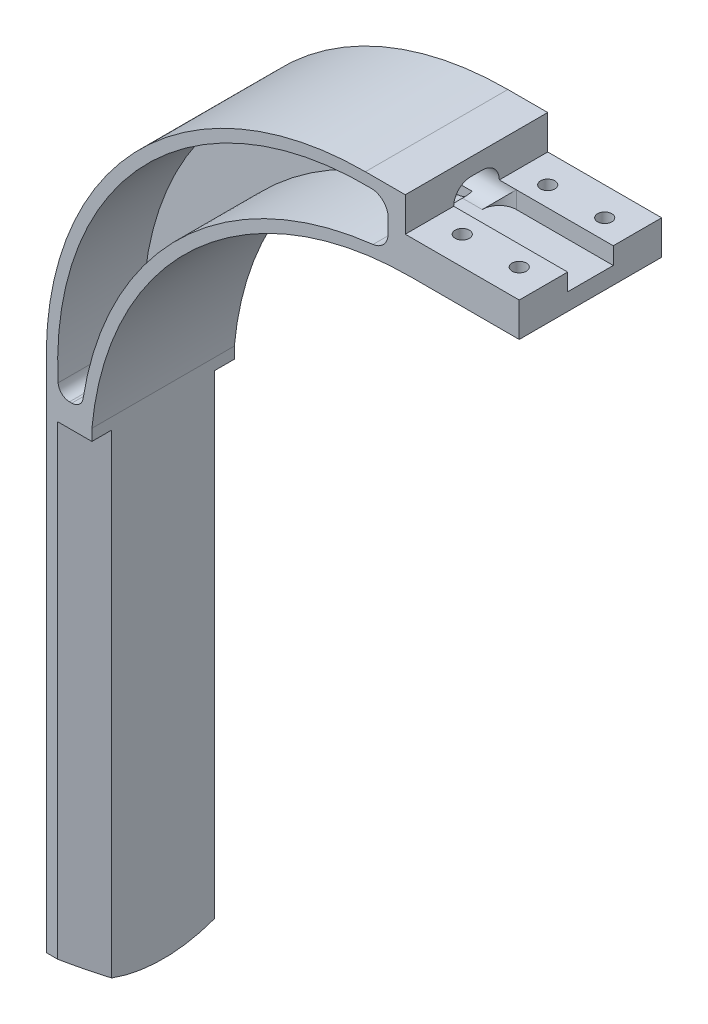
SolidWorks part; units mm, degrees
material "Сплав 2024"
ref_plane "Спереди" through (0, 0, 0) normal (0, 0, 1) x (1, 0, 0)
ref_plane "Сверху" through (0, 0, 0) normal (0, 1, 0) x (1, 0, 0)
ref_plane "Справа" through (0, 0, 0) normal (1, 0, 0) x (0, 0, -1)
sketch "Эскиз1" plane through (0, 0, 0) normal (0, 0, 1) x (1, 0, 0)
  line L0 (0, 0) -> (0, 95)
  line L1 (0, 0) -> (8, 0)
  line L2 (-20.7345, 150) -> (144.5665, 150) construction
  line L3 (83, 163.3115) -> (83, 122.0175) construction
  line L4 (8, 0) -> (8, 87)
  line L6 (83, 150) -> (56, 150)
  line L7 (83, 150) -> (83, 138)
  line L8 (83, 138) -> (64, 138)
  arc A0 (64, 138) -> (8, 87) centre (64, 81.7549) ccw
  arc A1 (56, 150) -> (0, 95) centre (56, 93.9909) ccw
  dimension "D1" = 95
  dimension "D2" = 87
  dimension "D3" = 150
  dimension "D4" = 83
  dimension "D5" = 8
  dimension "D6" = 12
  dimension "D7" = 27
  dimension "D8" = 19
extrude "Бобышка-Вытянуть1" add sketch "Эскиз1" along normal blind 25
sketch "Эскиз2" plane through (0, 0, 25) normal (0, 0, 1) x (1, 0, 0)
  line L1 (83, 150) -> (63, 150)
  line L2 (83, 150) -> (83, 144)
  line L3 (83, 144) -> (63, 144)
  line L4 (63, 150) -> (63, 144)
  dimension "D1" = 20
  dimension "D2" = 6
extrude "Вырез-Вытянуть1" cut sketch "Эскиз2" against normal through all
sketch "Эскиз5" plane through (0, 0, 0) normal (0, -1, 0) x (1, 0, 0)
  line L0 (8, 3.4641) -> (2, 0)
  line L1 (8, 25) -> (8, 0) construction
  line L2 (8, 3.4641) -> (10.1941, 4.7308)
  line L3 (2, 0) -> (8, 0)
  line L4 (8, 0) -> (8, 3.4641) construction
  line L5 (0, 25) -> (0, 0) construction
  line L6 (8, 12.5) -> (7.5, 12.5) construction
  line L7 (8, 25) -> (8, 0) construction
  line L8 (8, 25) -> (8, 21.5359) construction
  line L9 (2, 25) -> (8, 25)
  line L10 (8, 21.5359) -> (2, 25)
  line L11 (0, 0) -> (8, 0) construction
  line L12 (10.1941, 4.7308) -> (10.1941, 0)
  line L13 (8, 0) -> (64, 0) construction
  line L14 (10.1941, 0) -> (8, 0)
  line L15 (8, 21.5359) -> (10.1941, 20.2692)
  line L16 (10.1941, 20.2692) -> (10.1941, 25)
  line L17 (64, 25) -> (8, 25) construction
  line L18 (10.1941, 25) -> (8, 25)
  dimension "D1" = 2
  dimension "D2" = 60
extrude "Вырез-Вытянуть2" cut sketch "Эскиз5" against normal blind 85
sketch "Эскиз6" plane through (0, 0, 0) normal (-1, 0, 0) x (0, 0, 1)
  line L0 (12.5, 0) -> (12.5, 16.6862) construction
  line L1 (25, 0) -> (0, 0) construction
  line L2 (12.5, -11.9161) -> (12.5, 92.5) construction
  line L3 (10, -11.9161) -> (10, 92.5)
  line L4 (15, -11.9161) -> (15, 92.5)
  line L5 (25, 95) -> (0, 95) construction
  arc A0 (10, -11.9161) -> (15, -11.9161) centre (12.5, -11.9161) ccw
  arc A1 (15, 92.5) -> (10, 92.5) centre (12.5, 92.5) ccw
  point P7 (12.5, 40.292)
  dimension "D1" = 5
extrude "Вырез-Вытянуть4" cut sketch "Эскиз6" against normal blind 5
sketch "Эскиз3" plane through (0, 0, 25) normal (0, 0, -1) x (-1, 0, 0)
  line L0 (-60, 147.8517) -> (-60, 139.8625)
  line L1 (-63, 150) -> (-63, 144) construction
  line L2 (-6.2158, 89.0676) -> (-2.2158, 89.0676)
  arc A4 (-60, 147.8517) -> (-2.2158, 89.0676) centre (-56, 93.9909) cw
  arc A5 (-60, 139.8625) -> (-6.2158, 89.0676) centre (-64, 81.7549) cw
  arc A6 (0, 95) -> (-56, 150) centre (-56, 93.9909) ccw construction
  arc A7 (-8, 87) -> (-64, 138) centre (-64, 81.7549) ccw construction
  dimension "D1" = 2
  dimension "D2" = 2
  dimension "D3" = 3
  dimension "D4" = 4
extrude "Вырез-Вытянуть3" cut sketch "Эскиз3" along normal up to surface (15 mm away) up to face at (2.5, 46.25, 10)
fillet "Скругление3" radius 2 2 edges at (6.2158, 89.0676, 17.5) (2.2158, 89.0676, 20)
fillet "Скругление4" radius 3 2 edges at (60, 147.8517, 17.5) (60, 139.8625, 17.5)
ref_plane "Плоскость1" through (0, 10, 0) normal (0, 1, 0) x (1, 0, 0)
sketch "Эскиз8" plane through (0, 10, 0) normal (0, 1, 0) x (1, 0, 0)
  line L0 (0, -2) -> (1.5, -2)
  line L1 (0, -12.5) -> (0, 0) construction
  line L2 (1.5, -2) -> (1.5, -3)
  line L3 (3.5, -4) -> (5.5, -4)
  line L4 (5.5, -4) -> (5.5, -8)
  line L5 (5.5, -8) -> (0, -8)
  line L6 (0, -8) -> (0, -2)
  line L7 (56, 0) -> (0, 0) construction
  line L8 (2.0115, -10) -> (0, -10) construction
  line L9 (1.5, -3) -> (3.5, -3)
  line L10 (3.5, -3) -> (3.5, -4)
  line L11 (8, -25) -> (8, 0) construction
  line L12 (8, -12.5) -> (6.1534, -12.5) construction
  line L13 (3.5, -22) -> (3.5, -21)
  line L14 (1.5, -22) -> (3.5, -22)
  line L15 (0, -17) -> (0, -23)
  line L16 (5.5, -17) -> (0, -17)
  line L17 (5.5, -21) -> (5.5, -17)
  line L18 (3.5, -21) -> (5.5, -21)
  line L19 (1.5, -23) -> (1.5, -22)
  line L20 (0, -23) -> (1.5, -23)
  dimension "D1" = 2
  dimension "D2" = 2
  dimension "D3" = 4
  dimension "D4" = 1
  dimension "D5" = 1.5
  dimension "D6" = 2
  dimension "D7" = 2.5
extrude "Вырез-Вытянуть6" cut sketch "Эскиз8" along normal blind 75
sketch "Эскиз9" plane through (0, 144, 0) normal (0, 1, 0) x (1, 0, 0)
  line L0 (83, 0) -> (63, -25) construction
  line L1 (83, 0) -> (83, -25) construction
  line L2 (68, -5) -> (78, -5) construction
  line L3 (68, -5) -> (68, -20) construction
  line L4 (68, -20) -> (78, -20) construction
  line L5 (78, -5) -> (78, -20) construction
  line L6 (68, -5) -> (78, -20) construction
  line L7 (68, -20) -> (78, -5) construction
  line L8 (63, 0) -> (83, 0) construction
  point P4 (73, -12.5)
  dimension "D1" = 5
  dimension "D2" = 5
hole_wizard "Отверстие обработанное метчиком M3x0.51" positions "Эскиз11" profile "Эскиз10" tap size "M3x0.5" standard "Ansi Metric" end condition up to next
sketch "Эскиз11" plane through (19.192, 144, 18.7997) normal (0, 1, 0) x (1, 0, 0)
  point P0 (48.808, 13.7997)
  point P3 (58.808, 13.7997)
  point P6 (58.808, -1.2003)
  point P9 (48.808, -1.2003)
sketch "Эскиз10" plane through (68, 144, 5) normal (1, 0, 0) x (0, 0, 1)
  line L0 (0, 0) -> (0, 6)
  line L1 (0, 6) -> (1.25, 6)
  line L2 (1.25, 6) -> (1.25, 0)
  line L5 (1.25, 0) -> (0, 0)
  line L11 (0, -6.35) -> (0, 107.95) construction
  dimension "Диаметр резьбы" = 2.5
  dimension "Глубина проходного сверла" = 6
sketch "Эскиз12" plane through (0, 0, 0) normal (-1, 0, 0) x (0, 0, 1)
  line L0 (12.5, 0) -> (12.5, 6.3491) construction
  line L1 (10, 0) -> (15, 0) construction
  line L3 (0, 3.302) -> (0, 0)
  line L4 (0, 95) -> (0, 0) construction
  line L5 (0, 0) -> (12.5, 0)
  line L6 (12.5, 0) -> (25, 0)
  line L7 (25, 0) -> (25, 3.302)
  line L8 (25, 95) -> (25, 0) construction
  arc A0 (0, 3.302) -> (25, 3.302) centre (12.5, 26.1) ccw
  dimension "D1" = 52
  dimension "D2" = 26.1
extrude "Вырез-Вытянуть7" cut sketch "Эскиз12" against normal up to next
sketch "Эскиз13" plane through (0, 144, 0) normal (0, 1, 0) x (1, 0, 0)
  line L0 (83, -12.5) -> (63, -12.5) construction
  line L1 (83, 0) -> (83, -25) construction
  line L2 (63, 0) -> (63, -25) construction
  line L4 (63, -8.5) -> (83, -8.5)
  line L5 (63, -8.5) -> (63, -16.5)
  line L6 (63, -16.5) -> (83, -16.5)
  line L7 (83, -8.5) -> (83, -16.5)
  line L8 (63, -8.5) -> (83, -16.5) construction
  line L9 (63, -16.5) -> (83, -8.5) construction
  point P6 (73, -12.5)
  dimension "D1" = 8
extrude "Вырез-Вытянуть8" cut sketch "Эскиз13" against normal blind 3
fillet "Скругление8" radius 3 2 edges at (63, 142.5, 8.5) (63, 142.5, 16.5)
sketch "Эскиз14" plane through (83, 0, 0) normal (1, 0, 0) x (0, 0, -1)
  line L0 (-12.5, 141) -> (-12.5, 154.1514) construction
  line L1 (-16.5, 141) -> (-8.5, 141) construction
  line L4 (-13.5, 144) -> (-11.5, 144) construction
  line L5 (-13.5, 147) -> (-11.5, 147)
  line L6 (-13.5, 141) -> (-11.5, 141)
  line L7 (-16.5, 141) -> (-16.5, 144) construction
  arc A0 (-13.5, 147) -> (-13.5, 141) centre (-13.5, 144) ccw
  arc A1 (-11.5, 141) -> (-11.5, 147) centre (-11.5, 144) ccw
  point P5 (-12.5, 144)
  dimension "D1" = 6
extrude "Вырез-Вытянуть9" cut sketch "Эскиз14" against normal blind 28
sketch "Эскиз15" plane through (0, 0, 0) normal (-1, 0, 0) x (0, 0, 1)
  line L0 (12.5, 92.5) -> (12.5, 85.5) construction
  line L1 (15, 92.5) -> (15, 85.5)
  line L2 (10, 92.5) -> (10, 85.5)
  line L3 (15, 0.2205) -> (15, 89.1366) construction
  arc A0 (15, 92.5) -> (10, 92.5) centre (12.5, 92.5) ccw
  arc A1 (10, 85.5) -> (15, 85.5) centre (12.5, 85.5) ccw
  point P3 (12.5, 89)
  dimension "D1" = 7
extrude "Вырез-Вытянуть10" cut sketch "Эскиз15" against normal blind 6
sketch "Эскиз19" plane through (0, 0, 0) normal (-1, 0, 0) x (0, 0, 1)
  line L0 (10, 85.5) -> (10, 0.2205) construction
  line L1 (15, 92.5) -> (15, 0.2205) construction
  line L2 (10, 10.1) -> (10, 0.2205)
  line L3 (15, 10.1) -> (15, 0.2205)
  line L4 (10, 10.1) -> (15, 10.1)
  arc A0 (10, 0.2205) -> (15, 0.2205) centre (12.5, 26.1) ccw construction
  arc A1 (10, 0.2205) -> (15, 0.2205) centre (12.5, 26.1) ccw
  dimension "D1" = 16
extrude "Бобышка-Вытянуть2" add sketch "Эскиз19" against normal up to surface (5 mm away) up to face at (5, 42.2051, 12.5)
sketch "Эскиз16" plane through (0, 0, 0) normal (-1, 0, 0) x (0, 0, 1)
  line L0 (25, 5.1) -> (0, 5.1) construction
  line L1 (25, 95) -> (25, 3.302) construction
  line L3 (0, 95) -> (0, 3.302) construction
  arc A0 (0, 3.302) -> (25, 3.302) centre (12.5, 26.1) ccw construction
  point P4 (12.5, 0.1)
  dimension "D1" = 5
hole_wizard "Отверстие обработанное метчиком M3x0.52" positions "Эскиз18" profile "Эскиз17" tap size "M3x0.5" standard "Ansi Metric"
sketch "Эскиз18" plane through (0, 0, 0) normal (-1, 0, 0) x (0, 0, 1)
  line L1 (25, 5.1) -> (0, 5.1) construction
  point P5 (12.5, 5.1)
sketch "Эскиз17" plane through (0, 5.1, 12.5) normal (0, 1, 0) x (0, 0, 1)
  line L0 (0, 0) -> (0, 4.7511)
  line L1 (0, 4.7511) -> (1.25, 4)
  line L2 (1.25, 4) -> (1.25, 0)
  line L5 (1.25, 0) -> (0, 0)
  line L10 (0, 4.7511) -> (-1.25, 4) construction
  line L11 (0, -6.35) -> (0, 107.95) construction
  dimension "Диаметр сверла" = 2.5
  dimension "Глубина сверла" = 4
  dimension "Угол заточки сверла" = 118
cosmetic thread "Отверстие резьбы1" parameters "D1"=4, "D2"=3
